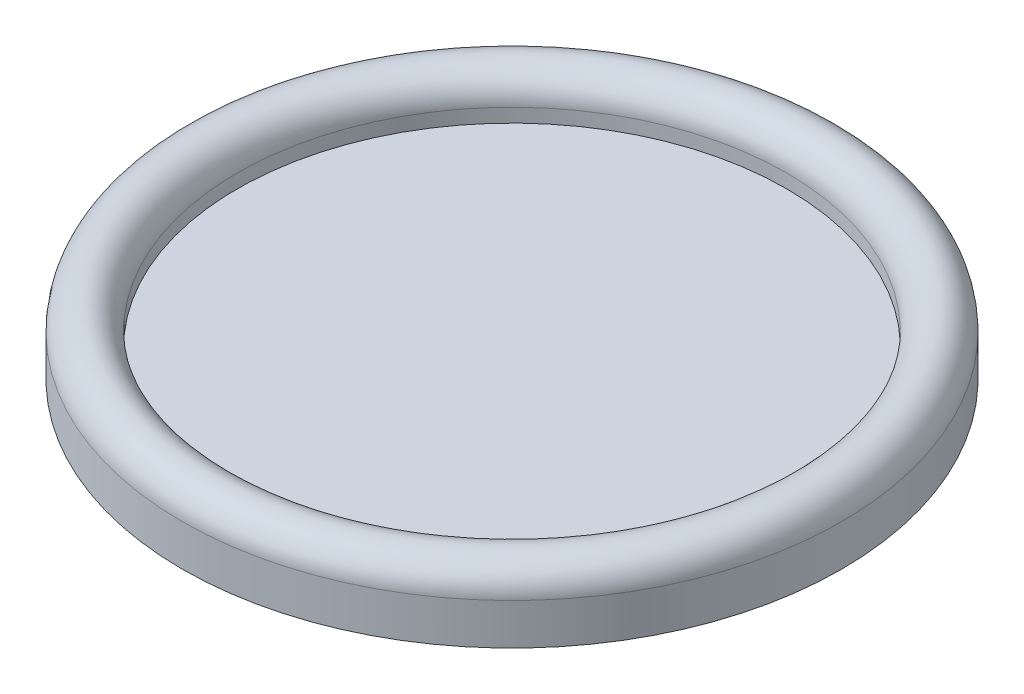
SolidWorks part; units mm, degrees
ref_plane "Front Plane" through (0, 0, 0) normal (0, 0, 1) x (1, 0, 0)
ref_plane "Top Plane" through (0, 0, 0) normal (0, 1, 0) x (1, 0, 0)
ref_plane "Right Plane" through (0, 0, 0) normal (1, 0, 0) x (0, 0, -1)
sketch "Sketch1" plane through (0, 0, 0) normal (0, 0, 1) x (1, 0, 0)
  line L0 (0, 0) -> (-76.2, 0)
  line L1 (-76.2, 0) -> (-76.2, 9.525)
  line L2 (-63.5, 9.525) -> (-63.5, 6.35)
  line L3 (-63.5, 6.35) -> (0, 6.35)
  line L4 (0, 6.35) -> (0, 0)
  line L5 (0, 0) -> (0, -13.5772)
  line L6 (0, -13.5772) -> (5.0763, -13.5772)
  arc A0 (-76.2, 9.525) -> (-63.5, 9.525) centre (-69.85, 9.525) cw
  arc A1 (0, -13.5772) -> (-76.2, 0) centre (0, 207.0416) cw
  point P11 (5.0763, -13.5772)
  point P12 (0, 0)
  dimension "D1" = 6.35
  dimension "D2" = 3.175
  dimension "D3" = 12.7
  dimension "D4" = 76.2
  dimension "D5" = 13.5772
revolve "Revolve2" add sketch "Sketch1" angle 360 about L4 region at (-28.696, -5.4455, 0) region at (-43.7018, 4.4769, 0)
